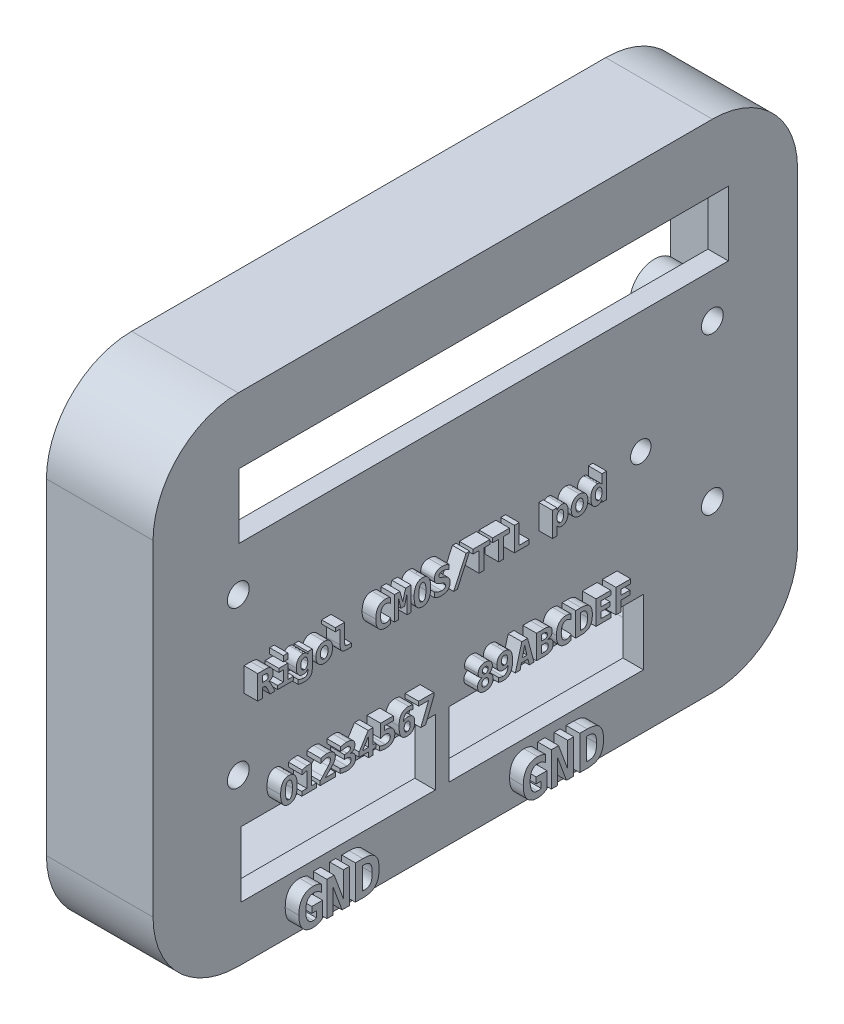
SolidWorks part; units mm, degrees
ref_plane "Front Plane" through (0, 0, 0) normal (0, 0, 1) x (1, 0, 0)
ref_plane "Top Plane" through (0, 0, 0) normal (0, 1, 0) x (1, 0, 0)
ref_plane "Right Plane" through (0, 0, 0) normal (1, 0, 0) x (0, 0, -1)
sketch "Sketch1" plane through (0, 0, 0) normal (1, 0, 0) x (0, 0, -1)
  line L0 (-6, 0.25) -> (-75.53, 0.25)
  line L1 (-6, 0) -> (-75.53, 0)
  line L2 (0, -6) -> (0, -53.85)
  line L3 (-6, -59.85) -> (-75.53, -59.85)
  line L4 (-81.53, -6) -> (-81.53, -53.85)
  line L5 (-81.78, -6) -> (-81.78, -53.85)
  line L6 (-6, -60.1) -> (-75.53, -60.1)
  line L7 (0.25, -6) -> (0.25, -53.85)
  line L8 (-6, 3.25) -> (-75.53, 3.25)
  line L9 (-84.78, -6) -> (-84.78, -53.85)
  line L10 (-6, -63.1) -> (-75.53, -63.1)
  line L11 (3.25, -6) -> (3.25, -53.85)
  line L12 (-6, 3.5) -> (-75.53, 3.5)
  line L13 (-85.03, -6) -> (-85.03, -53.85)
  line L14 (-6, -63.35) -> (-75.53, -63.35)
  line L15 (3.5, -6) -> (3.5, -53.85)
  line L16 (-6, 6.5) -> (-75.53, 6.5)
  line L17 (-88.03, -6) -> (-88.03, -53.85)
  line L18 (-6, -66.35) -> (-75.53, -66.35)
  line L19 (6.5, -6) -> (6.5, -53.85)
  line L20 (-75.45, -3.18) -> (-75.45, -12.68)
  line L21 (-75.2, -3.43) -> (-3.9, -3.43)
  line L22 (-75.2, -3.43) -> (-75.2, -12.43)
  line L23 (-75.2, -12.43) -> (-3.9, -12.43)
  line L24 (-3.9, -3.43) -> (-3.9, -12.43)
  line L25 (-75.45, -12.68) -> (-3.65, -12.68)
  line L26 (-3.65, -3.18) -> (-3.65, -12.68)
  line L27 (-75.45, -3.18) -> (-3.65, -3.18)
  line L28 (-75.14, -48.8) -> (-46.64, -48.8)
  line L29 (-74.89, -49.05) -> (-46.89, -49.05)
  line L30 (-74.89, -49.05) -> (-74.89, -58.14)
  line L31 (-74.89, -58.14) -> (-46.89, -58.14)
  line L32 (-46.89, -49.05) -> (-46.89, -58.14)
  line L33 (-44.36, -49.05) -> (-16.36, -49.05)
  line L34 (-44.36, -49.05) -> (-44.36, -58.14)
  line L35 (-44.36, -58.14) -> (-16.36, -58.14)
  line L36 (-16.36, -49.05) -> (-16.36, -58.14)
  line L37 (-46.64, -48.8) -> (-46.64, -58.39)
  line L38 (-75.14, -58.39) -> (-46.64, -58.39)
  line L39 (-75.14, -48.8) -> (-75.14, -58.39)
  line L40 (-44.61, -48.8) -> (-16.11, -48.8)
  line L41 (-16.11, -48.8) -> (-16.11, -58.39)
  line L42 (-44.61, -58.39) -> (-16.11, -58.39)
  line L43 (-44.61, -48.8) -> (-44.61, -58.39)
  circle A0 centre (-6, -19.12) radius 1.6
  circle A1 centre (-6, -42.05) radius 1.6
  circle A2 centre (-75.53, -19.12) radius 1.6
  circle A3 centre (-75.53, -42.05) radius 1.6
  arc A4 (-75.53, -59.85) -> (-81.53, -53.85) centre (-75.53, -53.85) cw
  arc A5 (0, -53.85) -> (-6, -59.85) centre (-6, -53.85) cw
  arc A6 (-6, 0) -> (0, -6) centre (-6, -6) cw
  arc A7 (-75.53, 0) -> (-81.53, -6) centre (-75.53, -6) ccw
  arc A8 (-75.53, 0.25) -> (-81.78, -6) centre (-75.53, -6) ccw
  arc A9 (-75.53, -60.1) -> (-81.78, -53.85) centre (-75.53, -53.85) cw
  arc A10 (0.25, -53.85) -> (-6, -60.1) centre (-6, -53.85) cw
  arc A11 (-6, 0.25) -> (0.25, -6) centre (-6, -6) cw
  arc A12 (-75.53, 3.25) -> (-84.78, -6) centre (-75.53, -6) ccw
  arc A13 (-75.53, -63.1) -> (-84.78, -53.85) centre (-75.53, -53.85) cw
  arc A14 (3.25, -53.85) -> (-6, -63.1) centre (-6, -53.85) cw
  arc A15 (-6, 3.25) -> (3.25, -6) centre (-6, -6) cw
  circle A16 centre (-75.53, -19.12) radius 3.6
  circle A17 centre (-6, -19.12) radius 3.6
  circle A18 centre (-6, -42.05) radius 3.6
  circle A19 centre (-75.53, -42.05) radius 3.6
  arc A20 (-75.53, 3.5) -> (-85.03, -6) centre (-75.53, -6) ccw
  arc A21 (-75.53, -63.35) -> (-85.03, -53.85) centre (-75.53, -53.85) cw
  arc A22 (3.5, -53.85) -> (-6, -63.35) centre (-6, -53.85) cw
  arc A23 (-6, 3.5) -> (3.5, -6) centre (-6, -6) cw
  arc A24 (-75.53, 6.5) -> (-88.03, -6) centre (-75.53, -6) ccw
  arc A25 (-75.53, -66.35) -> (-88.03, -53.85) centre (-75.53, -53.85) cw
  arc A26 (6.5, -53.85) -> (-6, -66.35) centre (-6, -53.85) cw
  arc A27 (-6, 6.5) -> (6.5, -6) centre (-6, -6) cw
  circle A28 centre (-16.5, -30.48) radius 1.5
  point P21 (0, -59.85)
  point P24 (0, 0)
  point P27 (-81.53, 0)
  dimension "D3" = 3.2
  dimension "D4" = 3.2
  dimension "D5" = 3.2
  dimension "D6" = 3.2
  dimension "D11" = 6
  dimension "D17" = 3
  dimension "D1" = 59.85
  dimension "D2" = 81.53
  dimension "D7" = 6
  dimension "D8" = 6
  dimension "D9" = 17.8
  dimension "D10" = 19.12
  dimension "D18" = 16.5
  dimension "D19" = 29.37
  dimension "D20" = 9
  dimension "D21" = 71.3
  dimension "D22" = 3.9
  dimension "D23" = 3.43
  dimension "D25" = 2.53
  dimension "D26" = 9.09
  dimension "D27" = 28
  dimension "D28" = 28
  dimension "D29" = 1.71
  dimension "D30" = 16.36
  dimension "D12" = 0.25
  dimension "D13" = 3
  dimension "D14" = 2
  dimension "D15" = 0.25
  dimension "D16" = 3
  dimension "D24" = 0.25
  dimension "D31" = 0.25
extrude "Boss-Extrude1" add sketch "Sketch1" along normal blind 3 contours L16 A24 L17 A25 L18 A26 L19 A27
extrude "Boss-Extrude4" add sketch "Sketch1<6>" against normal blind 12.64 contours A27 L16 A24 L17 A25 L18 A26 L19 L12 A23 L15 A22 L14 A21 L13 A20 region at (0, 1.9949, -1.9949)
sketch "Sketch1<6>" plane through (0, 0, 0) normal (1, 0, 0) x (0, 0, -1) same geometry as "Sketch1"
extrude "Cut-Extrude2" cut sketch "Sketch1<7>" against normal through all both and the other way through all contours A2 | A0 | A1 | A3
sketch "Sketch1<7>" plane through (0, 0, 0) normal (1, 0, 0) x (0, 0, -1) same geometry as "Sketch1"
extrude "Boss-Extrude5" add sketch "Sketch1<8>" against normal blind 5.5 contours A16 A2 | A17 A0 | A18 A1 | A19 A3 region at (0, -19.12, 79.0282) region at (0, -19.12, 9.4982) region at (0, -42.05, 9.4982) region at (0, -42.05, 79.0282)
sketch "Sketch1<8>" plane through (0, 0, 0) normal (1, 0, 0) x (0, 0, -1) same geometry as "Sketch1"
extrude "Cut-Extrude3" cut sketch "Sketch1<9>" against normal through all both and the other way through all contours L28 L37 L38 L39 | L40 L41 L42 L43 | A28 | L25 L26 L27 L20
sketch "Sketch1<9>" plane through (0, 0, 0) normal (1, 0, 0) x (0, 0, -1) same geometry as "Sketch1"
sketch "Sketch2" plane through (3, 0, 0) normal (1, 0, 0) x (0, 0, -1)
  text T0 "GND     GND" font "DejaVu Sans Mono" height 5
extrude "Boss-Extrude6" add sketch "Sketch2" along normal blind 2
sketch "Sketch3" plane through (3, 0, 0) normal (1, 0, 0) x (0, 0, -1)
  text T0 "O1234567  89ABCDEF" font "DejaVu Sans Mono" height 3.5
extrude "Boss-Extrude7" add sketch "Sketch3" along normal blind 2
sketch "Sketch4" plane through (3, 0, 0) normal (1, 0, 0) x (0, 0, -1)
  text T0 "Rigol CMOS/TTL pod" font "DejaVu Sans Mono" height 3.5
extrude "Boss-Extrude8" add sketch "Sketch4" along normal blind 2
